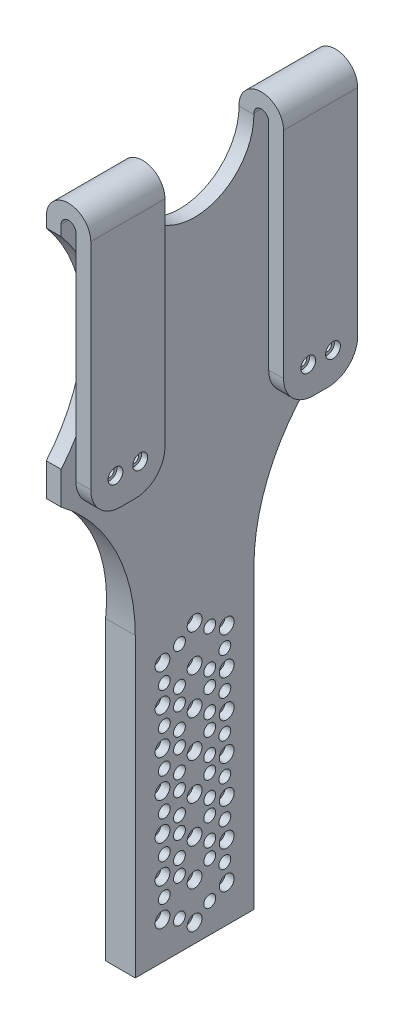
SolidWorks part; units mm, degrees
material "ABS"
ref_plane "前视基准面" through (0, 0, 0) normal (0, 0, 1) x (1, 0, 0)
ref_plane "上视基准面" through (0, 0, 0) normal (0, 1, 0) x (1, 0, 0)
ref_plane "右视基准面" through (0, 0, 0) normal (1, 0, 0) x (0, 0, -1)
other "Configuration Table"
sketch "草图1" plane through (0, 0, 0) normal (1, 0, 0) x (0, 0, -1)
  line L1 (-45, -45) -> (45, -45)
  line L2 (-45, -45) -> (-45, 45)
  line L3 (-45, 45) -> (45, 45)
  line L4 (45, -45) -> (45, 45)
  line L5 (-45, -45) -> (45, 45) construction
  line L6 (-45, 45) -> (45, -45) construction
  point P0 (0, 0)
  dimension "D1" = 90
  dimension "D2" = 90
extrude "凸台-拉伸1" add sketch "草图1" along normal blind 15
sketch "草图2" plane through (0, 0, 45) normal (0, 0, 1) x (1, 0, 0)
  line L0 (5, -45) -> (5, 37.5)
  line L1 (15, -45) -> (0, -45) construction
  line L3 (10, 37.5) -> (10, -45)
  line L4 (10, -45) -> (5, -45)
  line L5 (0, 45) -> (0, -45) construction
  line L6 (15, 45) -> (15, -45) construction
  line L8 (15, 45) -> (0, 45) construction
  line L9 (0, 37.5) -> (0, 45)
  line L10 (0, 45) -> (7.5, 45)
  line L11 (7.5, 45) -> (15, 45)
  line L12 (15, 45) -> (15, 37.5)
  line L13 (0, 37.5) -> (15, 37.5) construction
  arc A0 (10, 37.5) -> (5, 37.5) centre (7.5, 37.5) ccw
  arc A1 (0, 37.5) -> (15, 37.5) centre (7.5, 37.5) cw
  line M6 (0, 45) -> (0, -45)
  line M7 (0, -45) -> (15, -45)
  line M8 (15, -45) -> (15, 45)
  line M9 (15, 45) -> (0, 45)
  dimension "D3" = 7.5
  dimension "D1" = 5
  dimension "D2" = 5
extrude "切除-拉伸1" cut sketch "草图2" against normal through all contours A1 M6 M9 | A1 M9 M8 | A0 L13 | L13 L0 L3 M7 region at (7.5, -3.75, 45) region at (7.5, 38.561, 45) region at (1.6753, 43.3247, 45) region at (13.3247, 43.3247, 45)
sketch "草图3" plane through (15, 0, 0) normal (1, 0, 0) x (0, 0, -1)
  line L0 (45, 45) -> (-45, 45) construction
  line L1 (-20, -45) -> (20, -45)
  line L2 (-20, -45) -> (-20, 45)
  line L3 (-20, 45) -> (20, 45)
  line L4 (20, -45) -> (20, 45)
  line L5 (-20, -45) -> (20, 45) construction
  line L6 (-20, 45) -> (20, -45) construction
  line L7 (-45, 37.5) -> (-45, -45) construction
  point P0 (0, 0)
  dimension "D1" = 25
extrude "切除-拉伸2" cut sketch "草图3" against normal up to surface (10 mm away) up to face at (5, -3.75, 0)
fillet "圆角1" radius 10 4 edges at (12.5, -45, -45) (12.5, -45, -20) (12.5, -45, 20) (12.5, -45, 45)
sketch "草图4" plane through (5, 0, 0) normal (1, 0, 0) x (0, 0, -1)
  line L0 (-20, 44.5711) -> (-20, 37.1045)
  line L1 (-20, 37.5) -> (-20, -35) construction
  line L2 (-20, 44.5711) -> (20, 44.5711)
  line L3 (20, 44.5711) -> (20, 37.1045)
  line L4 (20, -35) -> (20, 37.5) construction
  line L5 (20, 37.1045) -> (-20, 37.1045) construction
  arc A0 (20, 37.1045) -> (-20, 37.1045) centre (0, 37.1045) cw
extrude "切除-拉伸3" cut sketch "草图4" against normal through all
sketch "草图6" plane through (0, 0, 0) normal (-1, 0, 0) x (0, 0, 1)
  line L0 (45, 37.5) -> (45, -45) construction
  line L1 (32.5, -955) -> (32.5, 49045) construction
  line L2 (45, 45) -> (20, 45) construction
  line L3 (0, -1000) -> (0, 49000) construction
  line L4 (-1000.7858, 0) -> (48999.2142, 0) construction
  line L5 (45, 33.9698) -> (45, -33.9698)
  line L6 (-45, 33.9698) -> (-45, -33.9698)
  arc A0 (45, 33.9698) -> (45, -33.9698) centre (84.9079, 0) ccw
  arc A1 (-45, 33.9698) -> (-45, -33.9698) centre (-84.9079, 0) cw
  point P10 (32.5, 45)
extrude "切除-拉伸4" cut sketch "草图6" against normal up to surface (10 mm away) and the other way blind 15 up to face at (10, -14.857, 32.5)
sketch "草图7" plane through (15, 0, 0) normal (1, 0, 0) x (0, 0, -1)
  line L1 (-35, -45) -> (-30, -45) construction
  line L2 (0, -1000) -> (0, 49000) construction
  line L4 (-32.5, -1045) -> (-32.5, 48955) construction
  line L5 (-45, -35) -> (-36.6667, -35) construction
  line L6 (-36.6667, -35) -> (-28.3333, -35) construction
  circle A2 centre (-36.6667, -35) radius 1.5
  circle A4 centre (-28.3333, -35) radius 1.5
  circle A5 centre (36.6667, -35) radius 1.5
  circle A6 centre (28.3333, -35) radius 1.5
  point P5 (-32.5, -45)
  dimension "D1" = 3
extrude "切除-拉伸5" cut sketch "草图7" against normal through all
sketch "草图8" plane through (15, 0, 0) normal (1, 0, 0) x (0, 0, -1)
  circle A1 centre (-36.6667, -35) radius 2.5
  circle A2 centre (-28.3333, -35) radius 2.5
  circle A3 centre (28.3333, -35) radius 2.5
  circle A4 centre (36.6667, -35) radius 2.5
  dimension "D1" = 5
  dimension "D2" = 5
  dimension "D3" = 5
  dimension "D4" = 5
extrude "切除-拉伸6" cut sketch "草图8" against normal blind 2
sketch "草图9" plane through (0, 0, 0) normal (0, 0, 1) x (1, 0, 0)
  line L0 (0, -45) -> (5, -45)
  line L1 (5, -45) -> (5, -195)
  line L2 (5, -195) -> (-5, -195)
  line L3 (-5, -195) -> (-5, -95)
  line L4 (-5, -95) -> (0, -45)
  dimension "D1" = 150
  dimension "D2" = 10
  dimension "D3" = 50
extrude "凸台-拉伸2" add sketch "草图9" along normal blind 45 and the other way blind 45
sketch "草图10" plane through (-5, 0, 0) normal (-1, 0, 0) x (0, 0, 1)
  line L0 (0, -1000) -> (0, 49000) construction
  line L1 (-1000, -176.2673) -> (49000, -176.2673) construction
  line L2 (-10.8253, -170.0173) -> (0, -176.2673) construction
  circle A2 centre (0, -176.2673) radius 12.5 construction
  circle A3 centre (0, -163.7673) radius 1.5
  circle A4 centre (0, -188.7673) radius 1.5
  circle A6 centre (-10.8253, -170.0173) radius 1.5
  circle A13 centre (-10.8253, -182.5173) radius 1.5
  circle A14 centre (10.8253, -182.5173) radius 1.5
  circle A15 centre (10.8253, -170.0173) radius 1.5
  dimension "D1" = 25
  dimension "D2" = 3
  dimension "D3" = 3
  dimension "D4" = 3
  dimension "D5" = 60
extrude "切除-拉伸7" cut sketch "草图10" against normal blind 50
sketch "草图11" plane through (-5, 0, 0) normal (-1, 0, 0) x (0, 0, 1)
  line L0 (-10.8253, -170.0173) -> (10.8253, -182.5173) construction
  line L1 (0, -1174.6348) -> (0, 48825.3652) construction
  line L2 (-5.1, -167.4339) -> (0, -176.2673) construction
  line L3 (5.1, -167.4339) -> (0, -176.2673) construction
  line L4 (-1000, -176.2673) -> (49000, -176.2673) construction
  circle A0 centre (0, -176.2673) radius 10.2 construction
  circle A1 centre (-5.1, -167.4339) radius 2
  circle A2 centre (10.2, -176.2673) radius 2
  circle A3 centre (5.1, -167.4339) radius 2
  circle A7 centre (5.1, -185.1008) radius 2
  circle A8 centre (-5.1, -185.1008) radius 2
  circle A9 centre (-10.2, -176.2673) radius 2
  dimension "D1" = 20.4
  dimension "D2" = 4
  dimension "D3" = 4
  dimension "D4" = 4
  dimension "D5" = 30
  dimension "D6" = 30
extrude "切除-拉伸8" cut sketch "草图11" against normal blind 50
sketch "草图13" plane through (5, 0, 0) normal (-1, 0, 0) x (0, 0, 1)
  circle A0 centre (0, -163.7673) radius 2.5
  circle A1 centre (10.8253, -170.0173) radius 2.5
  circle A2 centre (10.8253, -182.5173) radius 2.5
  circle A3 centre (0, -188.7673) radius 2.5
  circle A4 centre (-10.8253, -182.5173) radius 2.5
  circle A5 centre (-10.8253, -170.0173) radius 2.5
  dimension "D1" = 5
  dimension "D2" = 5
  dimension "D3" = 5
  dimension "D4" = 5
  dimension "D5" = 5
  dimension "D6" = 5
extrude "切除-拉伸9" cut sketch "草图13" along normal blind 3
pattern_linear "阵列(线性)3" count 6 spacing 12.5 along (0, 1, 0) of "切除-拉伸8", "切除-拉伸7", "切除-拉伸9"
sketch "草图14" plane through (-5, 0, 0) normal (-1, 0, 0) x (0, 0, 1)
  line L0 (-20, -195) -> (-20, -95)
  line L1 (-45, -195) -> (45, -195) construction
  line L2 (-45, -95) -> (45, -95) construction
  line L3 (-45, -45) -> (-45, -195)
  line L4 (-45, -195) -> (-20, -195)
  line L5 (0, -1000) -> (0, 49000) construction
  line L6 (45, -195) -> (20, -195)
  line L7 (45, -45) -> (45, -195)
  line L8 (20, -195) -> (20, -95)
  arc A0 (-45, -45) -> (-20, -95) centre (-82.5, -95) cw
  arc A1 (45, -45) -> (20, -95) centre (82.5, -95) ccw
  dimension "D1" = 25
extrude "切除-拉伸10" cut sketch "草图14" against normal through all
